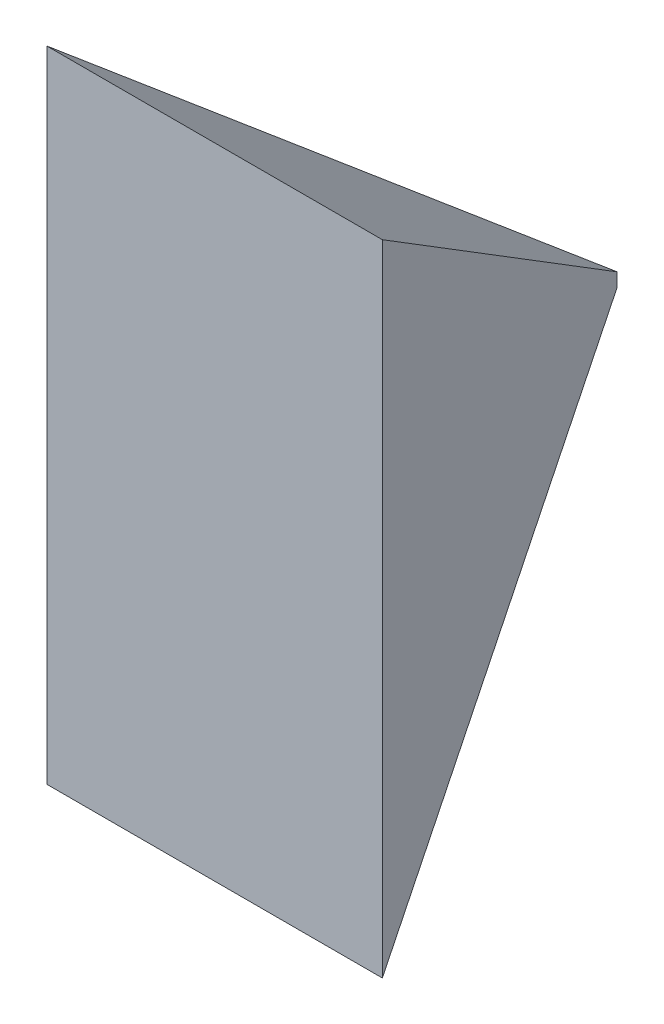
SolidWorks part; units mm, degrees
ref_plane "Front Plane" through (0, 0, 0) normal (0, 0, 1) x (1, 0, 0)
ref_plane "Top Plane" through (0, 0, 0) normal (0, 1, 0) x (1, 0, 0)
ref_plane "Right Plane" through (0, 0, 0) normal (1, 0, 0) x (0, 0, -1)
sketch "Sketch3" plane through (0, 0, 47.65) normal (0, 1, 0) x (1, 0, 0)
  line L0 (-12.5, 47.65) -> (0, 77.65)
  line L1 (0, 77.65) -> (12.5, 47.65)
  line L2 (12.5, 47.65) -> (-12.5, 47.65)
  point P5 (12.5, 47.65)
  point P6 (0, 47.65)
  point P8 (0, 77.65)
  dimension "D1" = 30
  dimension "D2" = 0
  dimension "D3" = 32.5
extrude "Boss-Extrude1" add sketch "Sketch3" along normal blind 47.65
sketch "Sketch4" plane through (0, 0, -4.2308) normal (1, 0, 0) x (0, 0, -1)
  line L0 (-4.2308, 47.65) -> (25.7692, 24.325)
  line L1 (25.7692, 47.65) -> (25.7692, 0) construction
  line L2 (25.7692, 24.325) -> (25.7692, 47.65)
  line L3 (-4.2308, 47.65) -> (25.7692, 47.65) construction
  line L4 (25.7692, 47.65) -> (-4.2308, 47.65)
  line L5 (-4.2308, 0) -> (25.7692, 0)
  line L6 (25.7692, 0) -> (25.7692, 23.325)
  line L7 (25.7692, 23.325) -> (-4.2308, 0)
  line L9 (-4.2308, 47.65) -> (-4.2308, 0) construction
  point P15 (55.7313, 27.8829)
  point P16 (50.7692, 27.1629)
  point P17 (-4.2308, 23.825)
  dimension "D1" = 1
  dimension "D2" = 0.5
extrude "Cut-Extrude1" cut sketch "Sketch4" against normal through all both and the other way through all
ref_plane "B Mid Plane" through (0, 23.825, 0) normal (0, -1, 0) x (-1, 0, 0)
